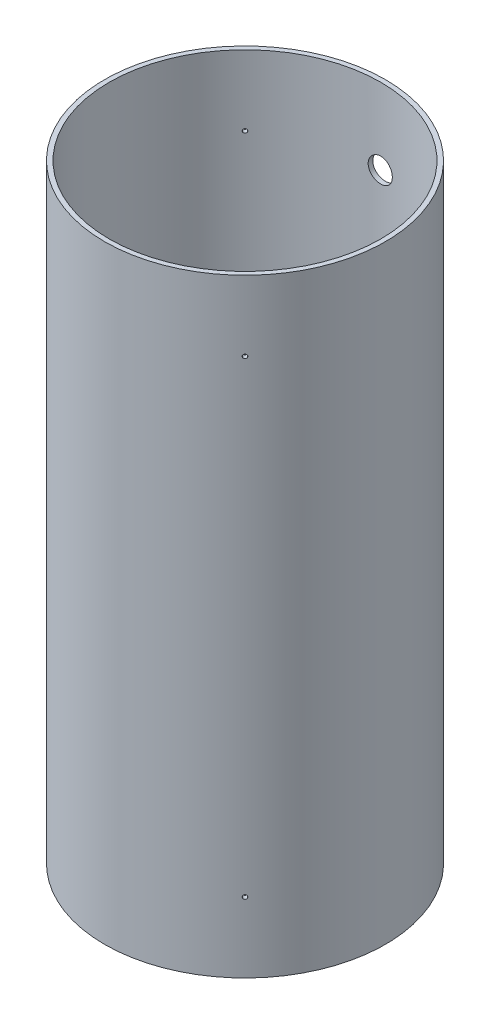
SolidWorks part; units mm, degrees
material "A-Glass Fiber"
ref_plane "Front Plane" through (0, 0, 0) normal (0, 0, 1) x (1, 0, 0)
ref_plane "Top Plane" through (0, 0, 0) normal (0, 1, 0) x (1, 0, 0)
ref_plane "Right Plane" through (0, 0, 0) normal (1, 0, 0) x (0, 0, -1)
sketch "Sketch1" plane through (0, 0, 0) normal (0, 1, 0) x (1, 0, 0)
  circle A0 centre (0, 0) radius 76.1746
  circle A1 centre (0, 0) radius 73.66
  dimension "D1" = 152.3492
  dimension "D2" = 147.32
extrude "Boss-Extrude1" add sketch "Sketch1" along normal blind 330.2
sketch "Sketch4" plane through (0, 0, 0) normal (0, 0, 1) x (1, 0, 0)
  line L0 (-76.1746, 0) -> (76.1746, 0) construction
  line L1 (76.1746, 330.2) -> (-76.1746, 330.2) construction
  line L2 (0, 330.2) -> (0, 0) construction
  line L3 (73.66, 330.2) -> (-73.66, 330.2) construction
  point P0 (0, 41.275)
  point P3 (0, 288.925)
  dimension "D1" = 41.275
  dimension "D2" = 41.275
hole_wizard "1/2 Clearance Hole5" positions "Sketch16" profile "Sketch17" hole size "1/2" standard "ANSI Inch"
sketch "Sketch16" plane through (0, 0, 0) normal (0, 0, 1) x (1, 0, 0)
  point P0 (0, 288.925)
sketch "Sketch17" plane through (0, 288.925, 0) normal (1, 0, 0) x (0, -1, 0)
  line L0 (0, 0) -> (0, 80.1345)
  line L1 (0, 80.1345) -> (6.5481, 76.2)
  line L2 (6.5481, 76.2) -> (6.5481, 0)
  line L5 (6.5481, 0) -> (0, 0)
  line L10 (0, 80.1345) -> (-6.5481, 76.2) construction
  line L11 (0, -6.35) -> (0, 107.95) construction
  dimension "Hole Dia." = 13.0962
  dimension "Hole Depth" = 76.2
  dimension "Drill Angle" = 118
hole_wizard "1/2 Clearance Hole7" positions "Sketch20" profile "Sketch21" hole size "1/2" standard "ANSI Inch"
sketch "Sketch20" plane through (0, 0, 0) normal (0, 0, 1) x (1, 0, 0)
  point P0 (0, 41.275)
sketch "Sketch21" plane through (0, 41.275, 0) normal (1, 0, 0) x (0, -1, 0)
  line L0 (0, 0) -> (0, 80.1345)
  line L1 (0, 80.1345) -> (6.5481, 76.2)
  line L2 (6.5481, 76.2) -> (6.5481, 0)
  line L5 (6.5481, 0) -> (0, 0)
  line L10 (0, 80.1345) -> (-6.5481, 76.2) construction
  line L11 (0, -6.35) -> (0, 107.95) construction
  dimension "Hole Dia." = 13.0962
  dimension "Hole Depth" = 76.2
  dimension "Drill Angle" = 118
ref_plane "Plane1" through (0, 0, 0) normal (-0.7071, 0, 0.7071) x (0.7071, 0, 0.7071)
sketch "Sketch23" plane through (0, 0, 0) normal (-0.7071, 0, 0.7071) x (0.7071, 0, 0.7071)
  line L0 (0, 0) -> (0, 330.2) construction
  line L1 (73.66, 330.2) -> (-73.66, 330.2) construction
  line L2 (-76.1746, 165.1) -> (76.1746, 165.1) construction
  line L3 (76.1746, 0) -> (76.1746, 330.2) construction
  circle A0 centre (0, 292.1) radius 1.0922
  circle A1 centre (0, 38.1) radius 1.0922
  point P12 (0, 165.1)
  dimension "D3" = 2.1844
  dimension "D1" = 127
  dimension "D2" = 127
extrude "Shear Scrrews" cut sketch "Sketch23" against normal through all
pattern_circular "CirPattern1" count 4 over 360 about axis through (0, 330.2, 0) along (0, -1, 0) of "Shear Scrrews"
equation "\"Mid_Coupler_Length\"= 13in"
equation "\"D1@Boss-Extrude1\"=\"Mid_Coupler_Length\""
equation "\"Shear_Screw_Coupler_Location\"= 4.5in"
equation "\"D1@Sketch23\"=\"Shear_Screw_Coupler_Location\"+0.5"
equation "\"Shear_Screw_Diameter\"= 0.086in"
equation "\"D2@Sketch23\"=\"Shear_Screw_Coupler_Location\"+0.5"
equation "\"D3@Sketch23\"=\"Shear_Screw_Diameter\""
